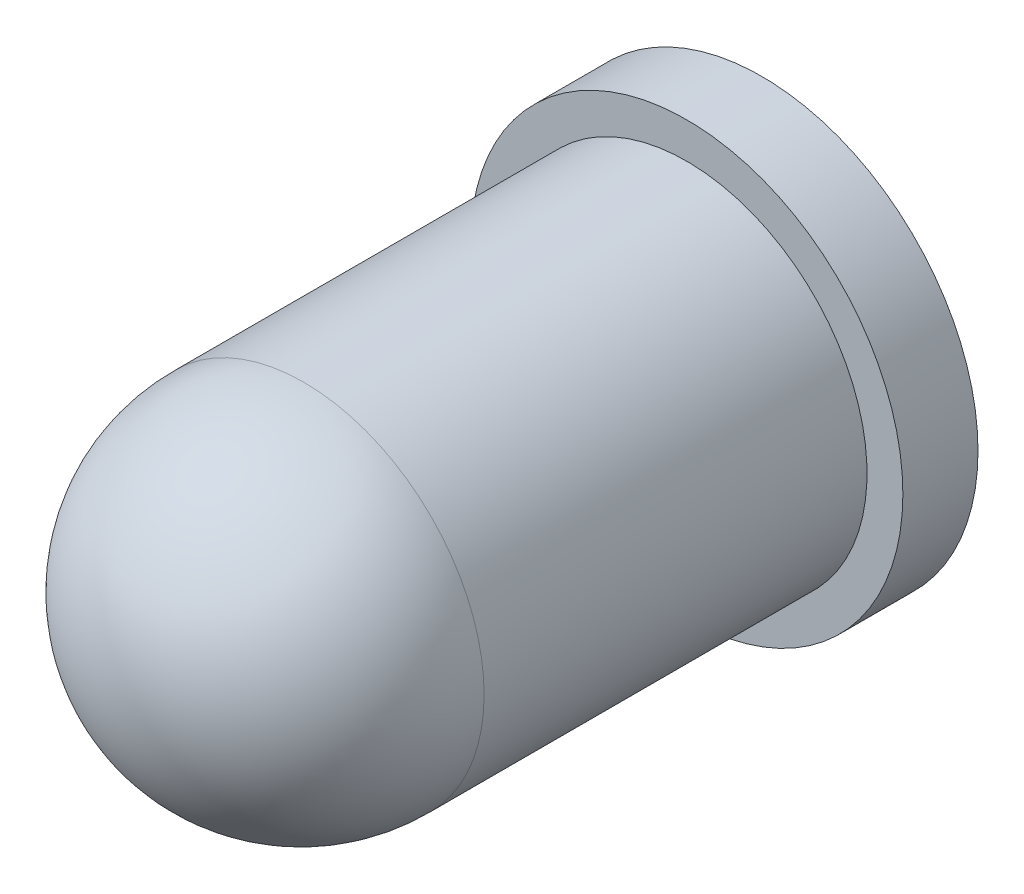
SolidWorks part; units mm, degrees
ref_plane "Front Plane" through (0, 0, 0) normal (0, 0, 1) x (1, 0, 0)
ref_plane "Top Plane" through (0, 0, 0) normal (0, 1, 0) x (1, 0, 0)
ref_plane "Right Plane" through (0, 0, 0) normal (1, 0, 0) x (0, 0, -1)
sketch "Sketch1" plane through (0, 0, 0) normal (0, 0, 1) x (1, 0, 0)
  circle A0 centre (0, 0) radius 2.5
  dimension "D1" = 5
extrude "Boss-Extrude1" add sketch "Sketch1" along normal blind 6.35
dome "Dome1" faces to dome 1 distance 2.54 reverse direction no elliptical dome no face at (2.5, 0, 6.35) parameters "D1"=2.54
sketch "Sketch2" plane through (0, 0, 0) normal (1, 0, 0) x (0, 0, -1)
  line L0 (-8.89, 0) -> (0, 0)
  arc A0 (-6.35, 2.5) -> (-6.35, -2.5) centre (-6.3897, 0) ccw construction
  dimension "D1" = 8.89
sketch "Sketch3" plane through (0, 0, 0) normal (0, 0, -1) x (-1, 0, 0)
  circle A0 centre (0, 0) radius 2.9972
  dimension "D1" = 5.9944
extrude "Boss-Extrude2" add sketch "Sketch3" against normal blind 1.0414
